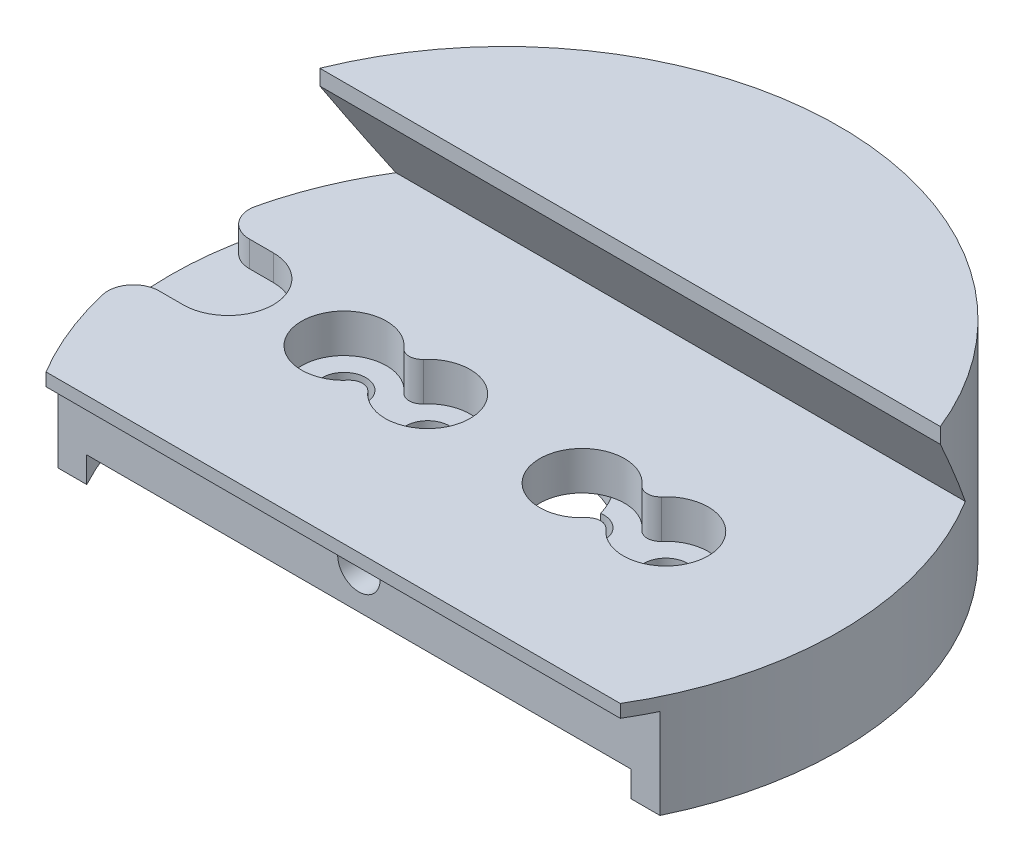
SolidWorks part; units mm, degrees
material "3.1355 (EN-AW 2024)"
ref_plane "Спереди" through (0, 0, 0) normal (0, 0, 1) x (1, 0, 0)
ref_plane "Сверху" through (0, 0, 0) normal (0, 1, 0) x (1, 0, 0)
ref_plane "Справа" through (0, 0, 0) normal (1, 0, 0) x (0, 0, -1)
sketch "Эскиз1" plane through (0, 0, 0) normal (0, 1, 0) x (1, 0, 0)
  circle A0 centre (0, 0) radius 26
  dimension "D1" = 52
extrude "Бобышка-Вытянуть1" add sketch "Эскиз1" along normal blind 14
sketch "Эскиз2" plane through (0, 0, 0) normal (1, 0, 0) x (0, 0, -1)
  line L0 (0, 14) -> (0, 0) construction
  line L1 (26, 14) -> (-26, 14) construction
  line L2 (13.6547, 6) -> (-13.6547, 6)
  line L3 (-13.6547, 6) -> (-9.7287, 12.8)
  line L4 (-9.7287, 12.8) -> (-9.7287, 14)
  line L5 (-9.7287, 14) -> (9.7287, 14)
  line L6 (0, 14) -> (0, 6) construction
  line L7 (13.6547, 6) -> (9.7287, 12.8)
  line L8 (9.7287, 12.8) -> (9.7287, 14)
  line L9 (-12.5, 8) -> (-12.5, 6) construction
  dimension "D1" = 8
  dimension "D2" = 1.2
  dimension "D3" = 60
  dimension "D4" = 13.6547
  dimension "D5" = 9.7287
  dimension "D6" = 2
  dimension "D7" = 12.5
extrude "Вырез-Вытянуть1" cut sketch "Эскиз2" against normal mid plane 60
sketch "Примерка" plane through (0, 0, 0) normal (1, 0, 0) x (0, 0, -1)
  line L0 (13.6547, 6) -> (-13.6547, 6) construction
  line L1 (-12.5, 14) -> (12.5, 14)
  line L2 (-12.5, 14) -> (-12.5, 6)
  line L3 (-12.5, 6) -> (12.5, 6)
  line L4 (12.5, 14) -> (12.5, 6)
  point P6 (0, 6)
  dimension "D1" = 8
  dimension "D2" = 25
sketch "Эскиз5" plane through (0, 0, 0) normal (0, -1, 0) x (1, 0, 0)
  line L2 (-22.1258, -15.6547) -> (22.1258, -15.6547)
  line L3 (-18.1915, -15.6547) -> (18.1915, -15.6547)
  circle A2 centre (0, 0) radius 24
  arc A3 (-18.1915, -15.6547) -> (18.1915, -15.6547) centre (0, 0) ccw
  dimension "D1" = 2
  dimension "D2" = 2
extrude "Вырез-Вытянуть3" cut sketch "Эскиз5" against normal offset from surface (12 mm away) 2 up to face at (0, 14, -17.8644)
sketch "Эскиз6" plane through (0, 6, 0) normal (0, 1, 0) x (1, 0, 0)
  line L1 (18.4208, 0) -> (-15.4735, 0) construction
  circle A0 centre (0, 0) radius 6 construction
  circle A1 centre (0, 0) radius 12.5 construction
  dimension "D1" = 12
  dimension "D2" = 25
hole_wizard "Цековка для винта с внутренним шестигранником M32" positions "Эскиз14" profile "Эскиз13" counterbore size "M3" standard "Ansi Metric" end condition up to next
sketch "Эскиз14" plane through (0, 6, 0) normal (0, 1, 0) x (1, 0, 0)
  line L0 (18.4208, 0) -> (-15.4735, 0) construction
  circle A0 centre (0, 0) radius 12.5 construction
  circle A1 centre (0, 0) radius 6 construction
  point P0 (-12.5, 0)
  point P6 (12.5, 0)
  point P20 (-6, 0)
  point P24 (6, 0)
sketch "Эскиз13" plane through (-12.5, 6, 0) normal (1, 0, 0) x (0, 0, 1)
  line L0 (0, 0) -> (0, 6)
  line L1 (0, 6) -> (1.7, 6)
  line L3 (1.7, 6) -> (1.7, 3)
  line L4 (1.7, 3) -> (3.3, 3)
  line L5 (3.3, 3) -> (3.3, 0)
  line L7 (3.3, 0) -> (0, 0)
  line L11 (0, -6.35) -> (0, 107.95) construction
  dimension "Диаметр сквозного отверстия" = 3.4
  dimension "Глубина сквозного отверстия" = 6
  dimension "Диаметр цековки" = 6.6
  dimension "Глубина цековки" = 3
sketch "Эскиз12" plane through (0, 0, 0) normal (0, -1, 0) x (1, 0, 0)
  circle A0 centre (0, 0) radius 26 construction
  circle A1 centre (0, 0) radius 26
  circle A3 centre (0, 0) radius 24
  dimension "D1" = 2
extrude "Бобышка-Вытянуть2" add sketch "Эскиз12" along normal blind 2
sketch "Эскиз17" plane through (0, 14, 0) normal (0, 1, 0) x (1, 0, 0)
  line L0 (-24.1112, -9.7287) -> (24.1112, -9.7287) construction
  line L1 (-24.1112, -9.7287) -> (24.1112, -9.7287)
  arc A0 (-24.1112, -9.7287) -> (24.1112, -9.7287) centre (0, 0) ccw construction
  arc A1 (-24.1112, -9.7287) -> (24.1112, -9.7287) centre (0, 0) ccw
extrude "Вырез-Вытянуть4" cut sketch "Эскиз17" against normal up to surface (8 mm away) up to face at (9.25, 6, 0)
fillet "Скругление2" radius 1 4 edges at (9.25, 4.5, -0.5723) (9.25, 4.5, 0.5723) (-9.25, 4.5, 0.5723) (-9.25, 4.5, -0.5723)
sketch "Эскиз18" plane through (0, 0, 0) normal (0, -1, 0) x (1, 0, 0)
  circle A0 centre (0, 0) radius 6
extrude "Вырез-Вытянуть5" cut sketch "Эскиз18" against normal blind 3
sketch "Эскиз19" plane through (0, 6, 0) normal (0, 1, 0) x (1, 0, 0)
  line L0 (-22.3137, -13.3453) -> (22.3137, -13.3453)
  line L1 (-22.1258, 13.6547) -> (22.1258, 13.6547) construction
  arc A0 (-22.1258, 13.6547) -> (22.1258, 13.6547) centre (0, 0) ccw construction
  arc A1 (-22.3137, -13.3453) -> (22.3137, -13.3453) centre (0, 0) ccw
  dimension "D1" = 27
extrude "Вырез-Вытянуть6" cut sketch "Эскиз19" against normal blind 10
sketch "Эскиз21" plane through (0, 0, 13.3453) normal (0, 0, 1) x (1, 0, 0)
  line L0 (0, 0) -> (0, 6) construction
  line L1 (19.9475, 0) -> (-19.9475, 0) construction
  line L2 (22.3137, 6) -> (-22.3137, 6) construction
  point P6 (0, 3)
  dimension "D1" = 3
hole_wizard "Отверстие обработанное метчиком M4x0.71" positions "Эскиз23" profile "Эскиз22" tap size "M4x0.7" standard "Ansi Metric"
sketch "Эскиз23" plane through (0, 0, 13.3453) normal (0, 0, 1) x (1, 0, 0)
  point P4 (0, 3)
sketch "Эскиз22" plane through (0, 3, 13.3453) normal (1, 0, 0) x (0, -1, 0)
  line L0 (0, 0) -> (0, 12.4914)
  line L1 (0, 12.4914) -> (1.65, 11.5)
  line L2 (1.65, 11.5) -> (1.65, 0)
  line L5 (1.65, 0) -> (0, 0)
  line L10 (0, 12.4914) -> (-1.65, 11.5) construction
  line L11 (0, -6.35) -> (0, 107.95) construction
  dimension "Диаметр сверла" = 3.3
  dimension "Глубина сверла" = 11.5
  dimension "Угол заточки сверла" = 118
cosmetic thread "Отверстие резьбы1" parameters "D1"=8, "D2"=4
sketch "Эскиз20" plane through (0, 0, 13.3453) normal (0, 0, 1) x (1, 0, 0)
  line L0 (0, 3.1198) -> (0, -5.6063) construction
  line L1 (22.3137, 6) -> (-22.3137, 6) construction
  line L2 (-25.2658, 5) -> (25.2658, 5)
  line L3 (-25.2658, 5) -> (-25.2658, -2)
  line L4 (-25.2658, -2) -> (25.2658, -2)
  line L5 (25.2658, 5) -> (25.2658, -2)
  line L6 (-25.2658, 5) -> (25.2658, -2) construction
  line L7 (-25.2658, -2) -> (25.2658, 5) construction
  line L8 (-22.3137, -2) -> (-19.9475, -2) construction
  point P3 (0, 1.5)
  dimension "D1" = 1
extrude "Вырез-Вытянуть7" cut sketch "Эскиз20" against normal blind 2
sketch "Эскиз24" plane through (0, 6, 0) normal (0, 1, 0) x (1, 0, 0)
  line L0 (-30.5, 0) -> (-21.5, 0) construction
  line L1 (-30.5, 3.5) -> (-21.5, 3.5)
  line L2 (-30.5, -3.5) -> (-21.5, -3.5)
  line L4 (0, 0) -> (-6.6582, 0) construction
  arc A0 (-22.1258, 13.6547) -> (-22.3137, -13.3453) centre (0, 0) ccw construction
  arc A1 (-30.5, 3.5) -> (-30.5, -3.5) centre (-30.5, 0) ccw
  arc A2 (-21.5, -3.5) -> (-21.5, 3.5) centre (-21.5, 0) ccw
  point P5 (-26, 0)
  dimension "D1" = 9
  dimension "D2" = 7
extrude "Вырез-Вытянуть8" cut sketch "Эскиз24" against normal blind 2
fillet "Скругление3" radius 2 2 edges at (-25.7633, 5, 3.5) (-25.7633, 5, -3.5)
